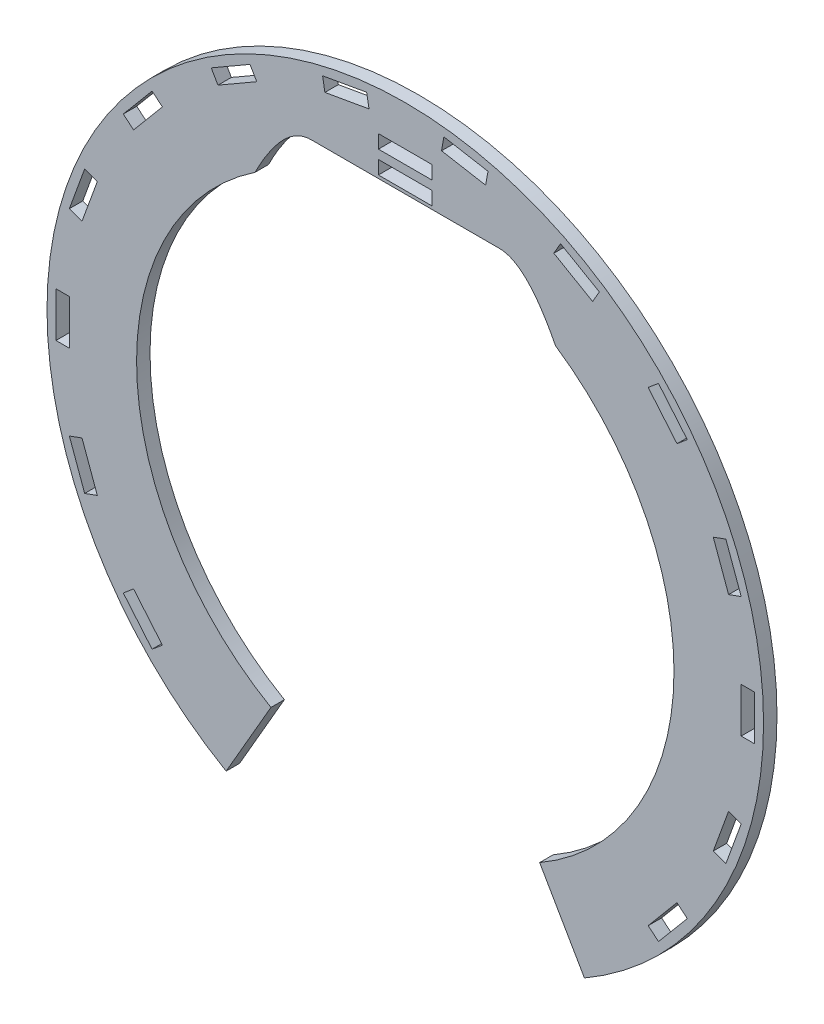
SolidWorks part; units mm, degrees
ref_plane "Přední rovina" through (0, 0, 0) normal (0, 0, 1) x (1, 0, 0)
ref_plane "Horní rovina" through (0, 0, 0) normal (0, 1, 0) x (1, 0, 0)
ref_plane "Pravá rovina" through (0, 0, 0) normal (1, 0, 0) x (0, 0, -1)
sketch "Skica1" plane through (0, 0, 0) normal (0, 0, 1) x (1, 0, 0)
  line L0 (-82.0154, 0) -> (100.8716, 0) construction
  line L1 (0, 71.1227) -> (0, -71.1227) construction
  line L2 (-40, -69.282) -> (-30, -51.9615)
  line L3 (50.2914, 87.1072) -> (-43.916, -76.0647) construction
  line L4 (40, -69.282) -> (-42.9451, 74.3831) construction
  line L5 (40, -69.282) -> (30, -51.9615)
  line L6 (30, 84.246) -> (30, -135.8986) construction
  line L7 (-30, 84.246) -> (-30, -135.8986) construction
  arc A0 (40, -69.282) -> (-40, -69.282) centre (0, 0) ccw
  arc A1 (30, -51.9615) -> (-30, -51.9615) centre (0, 0) ccw
  dimension "D4" = 80
  dimension "D1" = 30
  dimension "D2" = 30
  dimension "D3" = 20
extrude "Přidat vysunutím1" add sketch "Skica1" along normal blind 3
sketch "Skica3" plane through (0, 0, 3) normal (0, 0, 1) x (1, 0, 0)
  line L0 (-43.3301, 65.05) -> (-34.6699, 70.05)
  line L1 (-67.9025, -69.282) -> (98.6253, -69.282) construction
  line L3 (0, 0) -> (55.5524, 96.2196) construction
  line L4 (40, -69.282) -> (0, 0) construction
  line L5 (-6, 63) -> (6, 63)
  line L6 (0, 0) -> (96.2196, 55.5524) construction
  line L7 (0, 0) -> (111.1049, 0) construction
  line L8 (0, 0) -> (96.2196, -55.5524) construction
  line L9 (0, 0) -> (55.5524, -96.2196) construction
  line L10 (-6, 63) -> (-6, 66)
  line L11 (0, 0) -> (-55.5524, -96.2196) construction
  line L12 (0, 0) -> (-96.2196, -55.5524) construction
  line L13 (0, 0) -> (-111.1049, 0) construction
  line L14 (0, 0) -> (-96.2196, 55.5524) construction
  line L15 (0, 0) -> (-55.5524, 96.2196) construction
  line L16 (0, 0) -> (0, 111.1049) construction
  line L17 (0, 0) -> (0, -111.1049) construction
  line L18 (-6, 66) -> (6, 66)
  line L19 (6, 63) -> (6, 66)
  line L20 (-6, 63) -> (6, 66) construction
  line L21 (-6, 66) -> (6, 63) construction
  line L22 (-43.3301, 65.05) -> (-41.8301, 62.4519)
  line L23 (-34.6699, 70.05) -> (-33.1699, 67.4519)
  line L24 (-41.8301, 62.4519) -> (-33.1699, 67.4519)
  line L25 (-43.3301, 65.05) -> (-33.1699, 67.4519) construction
  line L26 (-34.6699, 70.05) -> (-41.8301, 62.4519) construction
  line L27 (-18.4686, 75.9468) -> (-8.6205, 77.6832)
  line L28 (-18.4686, 75.9468) -> (-17.9477, 72.9923)
  line L29 (-17.9477, 72.9923) -> (-8.0996, 74.7288)
  line L30 (-8.6205, 77.6832) -> (-8.0996, 74.7288)
  line L31 (8.6205, 77.6832) -> (18.4686, 75.9468)
  line L32 (8.6205, 77.6832) -> (8.0996, 74.7288)
  line L33 (8.0996, 74.7288) -> (17.9477, 72.9923)
  line L34 (18.4686, 75.9468) -> (17.9477, 72.9923)
  line L35 (34.6699, 70.05) -> (43.3301, 65.05)
  line L36 (34.6699, 70.05) -> (33.1699, 67.4519)
  line L37 (33.1699, 67.4519) -> (41.8301, 62.4519)
  line L38 (43.3301, 65.05) -> (41.8301, 62.4519)
  line L39 (56.5375, 53.9677) -> (62.9654, 46.3072)
  line L40 (56.5375, 53.9677) -> (54.2394, 52.0393)
  line L41 (54.2394, 52.0393) -> (60.6673, 44.3788)
  line L42 (62.9654, 46.3072) -> (60.6673, 44.3788)
  line L43 (71.5859, 31.376) -> (75.0061, 21.9791)
  line L44 (71.5859, 31.376) -> (68.7668, 30.35)
  line L45 (68.7668, 30.35) -> (72.187, 20.953)
  line L46 (75.0061, 21.9791) -> (72.187, 20.953)
  line L47 (78, 5) -> (78, -5)
  line L48 (78, 5) -> (75, 5)
  line L49 (75, 5) -> (75, -5)
  line L50 (78, -5) -> (75, -5)
  line L51 (75.0061, -21.9791) -> (71.5859, -31.376)
  line L52 (75.0061, -21.9791) -> (72.187, -20.953)
  line L53 (72.187, -20.953) -> (68.7668, -30.35)
  line L54 (71.5859, -31.376) -> (68.7668, -30.35)
  line L55 (62.9654, -46.3072) -> (56.5375, -53.9677)
  line L56 (62.9654, -46.3072) -> (60.6673, -44.3788)
  line L57 (60.6673, -44.3788) -> (54.2394, -52.0393)
  line L58 (56.5375, -53.9677) -> (54.2394, -52.0393)
  line L59 (43.3301, -65.05) -> (34.6699, -70.05) [skipped]
  line L60 (43.3301, -65.05) -> (41.8301, -62.4519) [skipped]
  line L61 (41.8301, -62.4519) -> (33.1699, -67.4519) [skipped]
  line L62 (34.6699, -70.05) -> (33.1699, -67.4519) [skipped]
  line L63 (18.4686, -75.9468) -> (8.6205, -77.6832) [skipped]
  line L64 (18.4686, -75.9468) -> (17.9477, -72.9923) [skipped]
  line L65 (17.9477, -72.9923) -> (8.0996, -74.7288) [skipped]
  line L66 (8.6205, -77.6832) -> (8.0996, -74.7288) [skipped]
  line L67 (-8.6205, -77.6832) -> (-18.4686, -75.9468) [skipped]
  line L68 (-8.6205, -77.6832) -> (-8.0996, -74.7288) [skipped]
  line L69 (-8.0996, -74.7288) -> (-17.9477, -72.9923) [skipped]
  line L70 (-18.4686, -75.9468) -> (-17.9477, -72.9923) [skipped]
  line L71 (-34.6699, -70.05) -> (-43.3301, -65.05) [skipped]
  line L72 (-34.6699, -70.05) -> (-33.1699, -67.4519) [skipped]
  line L73 (-33.1699, -67.4519) -> (-41.8301, -62.4519) [skipped]
  line L74 (-43.3301, -65.05) -> (-41.8301, -62.4519) [skipped]
  line L75 (-56.5375, -53.9677) -> (-62.9654, -46.3072)
  line L76 (-56.5375, -53.9677) -> (-54.2394, -52.0393)
  line L77 (-54.2394, -52.0393) -> (-60.6673, -44.3788)
  line L78 (-62.9654, -46.3072) -> (-60.6673, -44.3788)
  line L79 (-71.5859, -31.376) -> (-75.0061, -21.9791)
  line L80 (-71.5859, -31.376) -> (-68.7668, -30.35)
  line L81 (-68.7668, -30.35) -> (-72.187, -20.953)
  line L82 (-75.0061, -21.9791) -> (-72.187, -20.953)
  line L83 (-78, -5) -> (-78, 5)
  line L84 (-78, -5) -> (-75, -5)
  line L85 (-75, -5) -> (-75, 5)
  line L86 (-78, 5) -> (-75, 5)
  line L87 (-75.0061, 21.9791) -> (-71.5859, 31.376)
  line L88 (-75.0061, 21.9791) -> (-72.187, 20.953)
  line L89 (-72.187, 20.953) -> (-68.7668, 30.35)
  line L90 (-71.5859, 31.376) -> (-68.7668, 30.35)
  line L91 (-62.9654, 46.3072) -> (-56.5375, 53.9677)
  line L92 (-62.9654, 46.3072) -> (-60.6673, 44.3788)
  line L93 (-60.6673, 44.3788) -> (-54.2394, 52.0393)
  line L94 (-56.5375, 53.9677) -> (-54.2394, 52.0393)
  line L96 (6, 68) -> (-6, 68)
  line L97 (6, 68) -> (6, 71)
  line L98 (6, 71) -> (-6, 71)
  line L99 (-6, 68) -> (-6, 71)
  line L100 (6, 68) -> (-6, 71) construction
  line L101 (6, 71) -> (-6, 68) construction
  arc A0 (30, -51.9615) -> (-30, -51.9615) centre (0, 0) ccw construction
  point P0 (0, 63)
  point P3 (0, 0)
  point P4 (-40, -69.282)
  point P5 (40, -69.282)
  point P30 (0, 0)
  point P33 (0, 60)
  point P34 (0, 69.5)
  point P35 (-38.25, 66.2509)
  point P37 (-30, 51.9615)
  point P39 (-38.3657, 66.4513)
  point P112 (0, 0)
  dimension "D2" = 3
  dimension "D3" = 12
  dimension "D4" = 3
  dimension "D5" = 5
  dimension "D6" = 10
  dimension "D7" = 3
  dimension "D9" = 78
  dimension "D10" = 12
  dimension "D11" = 3
  dimension "D12" = 2
  dimension "D1" = 12
  dimension "D8" = 18
extrude "Odebrat vysunutím1" cut sketch "Skica3" against normal blind 3
sketch "Skica4" plane through (0, 0, 0) normal (0, 0, -1) x (-1, 0, 0)
  line L0 (0, 85.4839) -> (0, 30.8548) construction
  line L1 (-33.5345, 49.7538) -> (33.5345, 49.7538) construction
  line L2 (-21, 62.31) -> (21, 62.31)
  line L6 (-21, 83.0379) -> (-21, 33.4147) construction
  line L7 (21, 83.0379) -> (21, 33.4147) construction
  line L8 (-37.7575, 62.31) -> (42.834, 62.31) construction
  line L9 (-21, 49.7538) -> (-34.141, 62.8947) construction
  line L10 (-21, 62.31) -> (-27.1966, 62.31) construction
  line L11 (21, 49.7538) -> (35.1421, 63.8959) construction
  line L12 (-33.5345, 47.1737) -> (-33.5345, 65.3835) construction
  line L13 (-27.1966, 62.31) -> (-33.5345, 49.7538) construction
  line L14 (21, 62.31) -> (27.1966, 62.31) construction
  line L15 (27.1966, 62.31) -> (33.5345, 49.7538) construction
  line L16 (-33.5345, 49.7538) -> (33.5345, 49.7538)
  arc A0 (30, -51.9615) -> (-30, -51.9615) centre (0, 0) ccw construction
  spline S0 degree 2 poles (-21, 62.31) (-27.1966, 62.31) (-33.5345, 49.7538) knots 0 0 0 1 1 1
  spline S1 degree 2 poles (21, 62.31) (27.1966, 62.31) (33.5345, 49.7538) knots 0 0 0 1 1 1
  point P2 (0, 57.56)
  dimension "D1" = 45
  dimension "D2" = 45
extrude "Odebrat vysunutím3" cut sketch "Skica4" against normal blind 3 contours L2 S1 L16 S0
